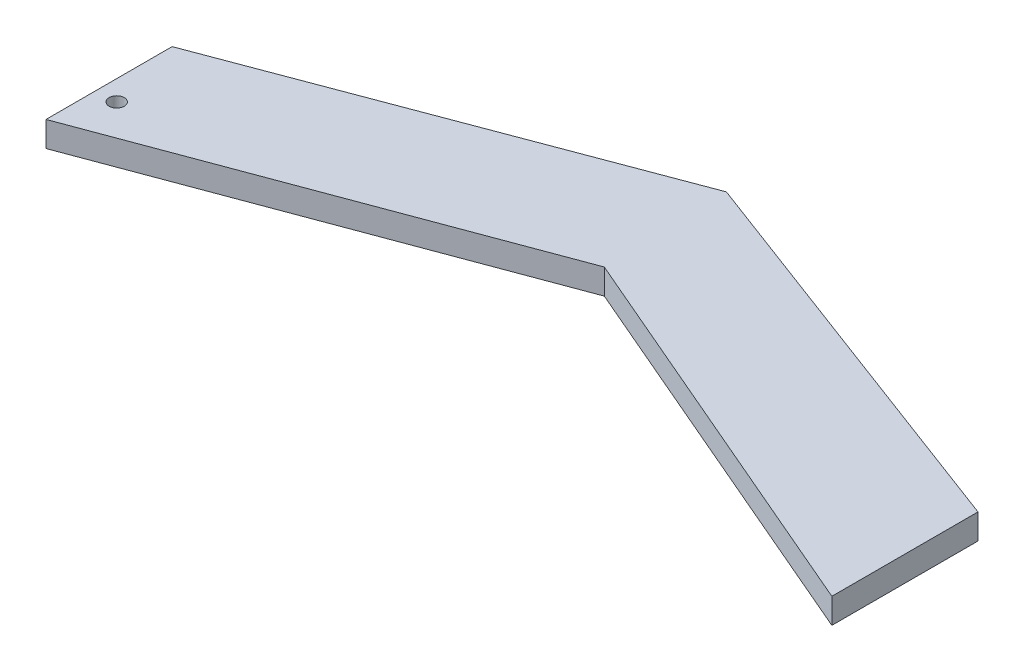
SolidWorks part; units mm, degrees
ref_plane "Front Plane" through (0, 0, 0) normal (0, 0, 1) x (1, 0, 0)
ref_plane "Top Plane" through (0, 0, 0) normal (0, 1, 0) x (1, 0, 0)
ref_plane "Right Plane" through (0, 0, 0) normal (1, 0, 0) x (0, 0, -1)
sketch "Sketch1" plane through (0, 0, 0) normal (0, 1, 0) x (1, 0, 0)
  line L0 (0, 0) -> (102.4509, 38.1)
  line L2 (0, 0) -> (0, 31.75)
  line L4 (202.8825, -5.0425) -> (202.8825, 31.75)
  line L6 (102.4509, 38.1) -> (202.8825, -5.0425)
  line L7 (0, 31.75) -> (101.4412, 69.85)
  line L8 (101.4412, 69.85) -> (202.8825, 31.75)
  point P5 (19.05, 8.3323)
  point P7 (102.9717, 59.0545)
  point P9 (0, 0)
  point P10 (0, 0)
  dimension "D1" = 202.8825
  dimension "D2" = 31.75
  dimension "D3" = 31.75
  dimension "D4" = 69.85
extrude "Boss-Extrude1" add sketch "Sketch1" along normal blind 6.35
sketch "Sketch3" plane through (0, 6.35, 0) normal (0, 1, 0) x (1, 0, 0)
  circle A1 centre (5.0844, 12.7175) radius 1.905 construction
  circle A5 centre (5.0844, 12.7175) radius 1.905
extrude "Cut-Extrude1" cut sketch "Sketch3" against normal through all
ref_plane "Plane1" through (101.4412, 0, 0) normal (-1, 0, 0) x (0, 0, 1)
